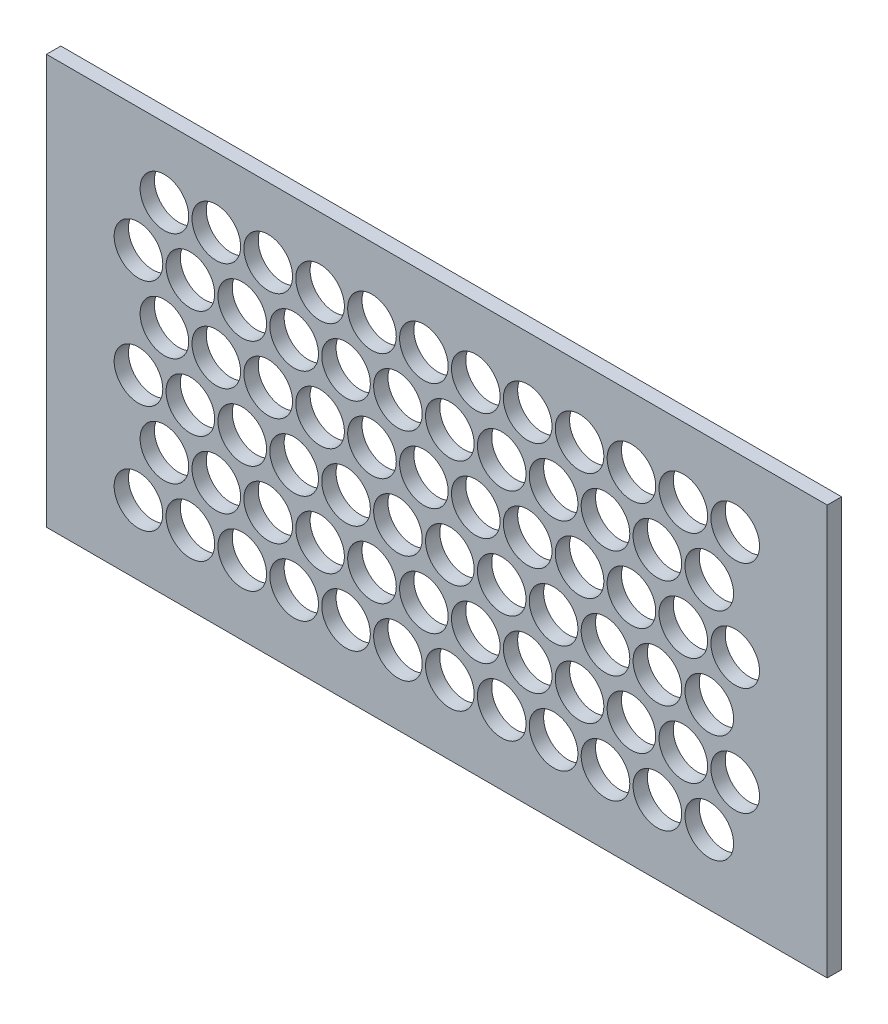
SolidWorks part; units mm, degrees
material "ABS"
ref_plane "X-Y Datum" through (0, 0, 0) normal (0, 0, 1) x (1, 0, 0)
ref_plane "X-Z Datum" through (0, 0, 0) normal (0, 1, 0) x (1, 0, 0)
ref_plane "Y-Z Datum" through (0, 0, 0) normal (1, 0, 0) x (0, 0, -1)
sketch "Sketch1" plane through (0, 0, 0) normal (0, 0, 1) x (1, 0, 0)
  line L1 (-143.025, 70.775) -> (143.025, 70.775)
  line L2 (-143.025, 70.775) -> (-143.025, -70.775)
  line L3 (-143.025, -70.775) -> (143.025, -70.775)
  line L4 (143.025, 70.775) -> (143.025, -70.775)
  line L5 (-143.025, 70.775) -> (143.025, -70.775) construction
  line L6 (-143.025, -70.775) -> (143.025, 70.775) construction
  line L13 (-173.025, -90.775) -> (173.025, -90.775)
  line L14 (-173.025, 90.775) -> (173.025, 90.775)
  line L15 (-173.025, 90.775) -> (-173.025, -90.775)
  line L16 (173.025, 90.775) -> (173.025, -90.775)
  line L17 (173.025, 70.775) -> (173.025, -70.775) construction
  line L18 (-143.025, 90.775) -> (143.025, 90.775) construction
  line L19 (-143.025, -90.775) -> (143.025, -90.775) construction
  line L20 (-173.025, 70.775) -> (-173.025, -70.775) construction
  line L21 (-132.25, -60) -> (-109.25, -60) construction
  circle A0 centre (-132.25, -60) radius 10.775
  circle A1 centre (-109.25, -60) radius 10.775 construction
  circle A2 centre (-120.75, -36) radius 10.775
  point P0 (0, 0)
  point P16 (-120.75, -60)
  point P17 (0, 0)
  dimension "D1" = 21.55
  dimension "D2" = 23
  dimension "D3" = 24
  dimension "D5" = 141.55
  dimension "D6" = 286.05
  dimension "D7" = 20
  dimension "D8" = 20
  dimension "D9" = 30
  dimension "D10" = 30
extrude "Boss-Extrude1" add sketch "Sketch1" along normal blind 6.35 contours A0 L3 L4 L1 L2 A2 | A2 | A0 | A0 L2 L3 | L1 L4 L3 L2 region at (2.4105, 0.9241, 0) region at (-140.6182, -68.3682, 0) region at (-132.25, -60, 0) region at (-169.1172, 0, 0) region at (-120.75, -36, 0)
sketch "Sketch3" plane through (0, 0, 6.35) normal (0, 0, 1) x (1, 0, 0)
  line L4 (143.025, 70.775) -> (-143.025, 70.775)
  line L5 (143.025, -70.775) -> (143.025, 70.775)
  line L6 (-143.025, -70.775) -> (143.025, -70.775)
  line L7 (-143.025, 70.775) -> (-143.025, -70.775)
  line L8 (143.025, 70.775) -> (-143.025, 70.775)
  line L9 (143.025, -70.775) -> (143.025, 70.775)
  line L10 (-143.025, -70.775) -> (143.025, -70.775)
  line L11 (-143.025, 70.775) -> (-143.025, -70.775)
  circle A1 centre (-120.75, -36) radius 10.775
  circle A2 centre (-120.75, -36) radius 10.775
  circle A3 centre (-132.25, -60) radius 10.775
  circle A4 centre (-132.25, -60) radius 10.775
  dimension "D1" = 0
  dimension "D2" = 0
  dimension "D3" = 0
extrude "Cut-Extrude1" cut sketch "Sketch3" against normal through all contours A4 region at (-132.25, -60, 6.35)
sketch "Sketch4" plane through (0, 0, 6.35) normal (0, 0, 1) x (1, 0, 0)
  line L4 (143.025, 70.775) -> (-143.025, 70.775)
  line L5 (143.025, -70.775) -> (143.025, 70.775)
  line L6 (-143.025, -70.775) -> (143.025, -70.775)
  line L7 (-143.025, 70.775) -> (-143.025, -70.775)
  line L8 (143.025, 70.775) -> (-143.025, 70.775)
  line L9 (143.025, -70.775) -> (143.025, 70.775)
  line L10 (-143.025, -70.775) -> (143.025, -70.775)
  line L11 (-143.025, 70.775) -> (-143.025, -70.775)
  circle A1 centre (-120.75, -36) radius 10.775
  circle A2 centre (-120.75, -36) radius 10.775
  circle A3 centre (-132.25, -60) radius 10.775
  circle A4 centre (-132.25, -60) radius 10.775
  dimension "D1" = 0
  dimension "D2" = 0
  dimension "D3" = 0
extrude "Cut-Extrude2" cut sketch "Sketch4" against normal through all contours A2 region at (-120.75, -36, 6.35)
pattern_linear "LPattern1" count 12 spacing 23 along (1, 0, 0) of "Cut-Extrude1", "Cut-Extrude2"
pattern_linear "LPattern2" count 3 spacing 48 along (0, 1, 0) of "LPattern1"
